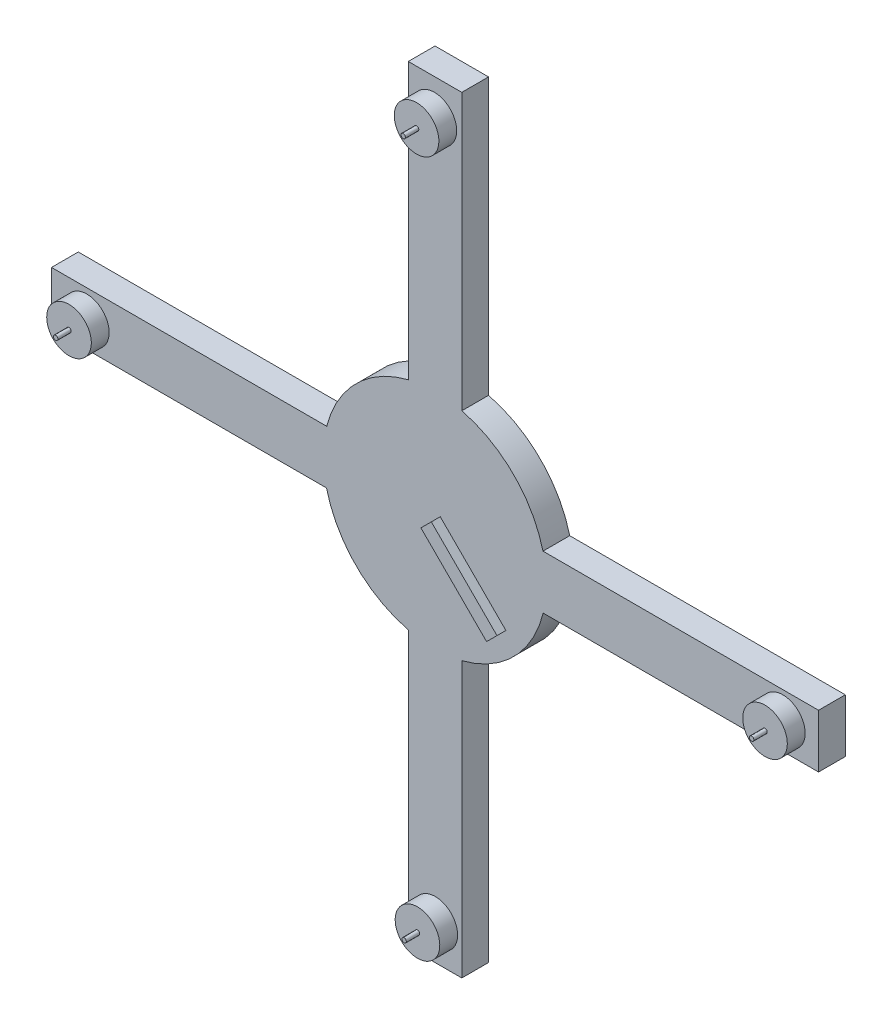
SolidWorks part; units mm, degrees
material "Nylon 101"
ref_plane "Front Plane" through (0, 0, 0) normal (0, 0, 1) x (1, 0, 0)
ref_plane "Top Plane" through (0, 0, 0) normal (0, 1, 0) x (1, 0, 0)
ref_plane "Right Plane" through (0, 0, 0) normal (1, 0, 0) x (0, 0, -1)
sketch "Sketch1" plane through (0, 0, 0) normal (0, 0, 1) x (1, 0, 0)
  line L0 (-30, 430) -> (30, 430)
  line L1 (30, 430) -> (30, 30)
  line L2 (30, 30) -> (430, 30)
  line L3 (430, 30) -> (430, -30)
  line L4 (430, -30) -> (30, -30)
  line L5 (30, -30) -> (30, -430)
  line L6 (30, -430) -> (-30, -430)
  line L7 (-30, -430) -> (-30, -30)
  line L8 (-30, -30) -> (-430, -30)
  line L9 (-430, -30) -> (-430, 30)
  line L10 (-430, 30) -> (-30, 30)
  line L11 (-30, 30) -> (-30, 430)
  circle A0 centre (-0.208, -0.5161) radius 125
  circle A1 centre (0, 0) radius 42.4264
  dimension "D3" = 250
  dimension "D1" = 400
  dimension "D2" = 60
extrude "Boss-Extrude1" add sketch "Sketch1" along normal blind 15 and the other way blind 15 contours L1 L0 L11 | A1 L1 L11 | A1 L4 L2 | L4 L3 L2 | L7 L6 L5 | A1 L10 L8 | A1 L7 L5 | L8 L7 | L5 L4 | L2 L1 | L11 L10 | L10 L9 L8 | A1 region at (0.0017, 276.6346, 0) region at (-0.006, 80.8479, 0) region at (-66.0265, 65.8286, 0) region at (65.8488, 65.7648, 0) region at (-81.2101, -0.0148, 0) region at (0, 0, 0) region at (-276.9962, 0.0041, 0) region at (81.0018, -0.0148, 0) region at (276.7882, 0.0041, 0) region at (-0.0059, -81.3649, 0) region at (-66.185, -66.2697, 0) region at (0.0017, -277.1507, 0) region at (66.0072, -66.2058, 0)
sketch "Sketch2" plane through (0, 0, 15) normal (0, 0, 1) x (1, 0, 0)
  line L0 (430, 30) -> (430, -30) construction
  circle A0 centre (390, 0) radius 25
  dimension "D1" = 50
  dimension "D2" = 40
extrude "Boss-Extrude2" add sketch "Sketch2" along normal blind 20
sketch "Sketch3" plane through (0, 0, 35) normal (0, 0, 1) x (1, 0, 0)
  circle A0 centre (390, 0) radius 2.5
  circle A1 centre (390, 0) radius 25 construction
  dimension "D1" = 5
extrude "Boss-Extrude3" add sketch "Sketch3" along normal blind 15
pattern_circular "CirPattern1" count 4 over 360 about axis through (-0.208, -0.5161, -15) along (0, 0, 1) of "Boss-Extrude2", "Boss-Extrude3"
sketch "Sketch4" plane through (0, 0, 15) normal (0, 0, 1) x (1, 0, 0)
  line L0 (-5.8347, -5.8347) -> (67.7881, -79.4575)
  line L1 (-5.8347, -5.8347) -> (5.8347, 5.8347)
  line L2 (67.7881, -79.4575) -> (79.4575, -67.7881)
  line L3 (5.8347, 5.8347) -> (79.4575, -67.7881)
  line L4 (430, -30) -> (121.2651, -30) construction
  point P6 (0, 0)
  point P9 (0, 0)
  point P11 (0, 0)
  dimension "D1" = 135
extrude "Boss-Extrude4" add sketch "Sketch4" along normal blind 10
